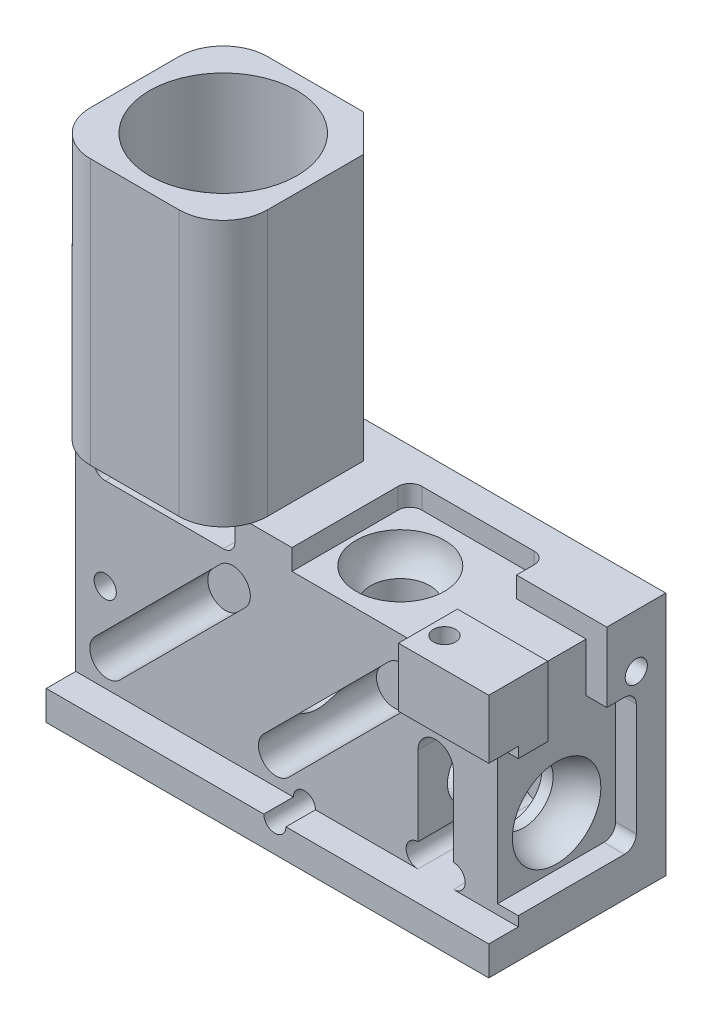
SolidWorks part; units mm, degrees
ref_plane "Front Plane" through (0, 0, 0) normal (0, 0, 1) x (1, 0, 0)
ref_plane "Top Plane" through (0, 0, 0) normal (0, 1, 0) x (1, 0, 0)
ref_plane "Right Plane" through (0, 0, 0) normal (1, 0, 0) x (0, 0, -1)
sketch "Sketch1" plane through (0, 0, 0) normal (0, 1, 0) x (1, 0, 0)
  line L1 (7.5, 3) -> (-7.5, 3)
  line L2 (7.5, 3) -> (7.5, -3)
  line L3 (7.5, -3) -> (-7.5, -3)
  line L4 (-7.5, 3) -> (-7.5, -3)
  line L5 (7.5, 3) -> (-7.5, -3) construction
  line L6 (7.5, -3) -> (-7.5, 3) construction
  point P0 (0, 0)
  dimension "D1" = 6
  dimension "D2" = 15
extrude "Main Body Ext" add sketch "Sketch1" along normal blind 8.3
sketch "Sketch8" plane through (0, 8.3, 0) normal (0, 1, 0) x (1, 0, 0)
  line L0 (-2.75, 3) -> (-1.5, 1.75)
  line L1 (-2.75, 3) -> (-7.5, 3)
  line L2 (-1.5, 1.75) -> (-1.5, -3)
  line L3 (-1.5, -3) -> (-7.5, -3)
  line L4 (-7.5, 3) -> (-7.5, -3)
  line L5 (-2.125, 2.375) -> (-7.5, -3) construction
  line L6 (-1.5, -3) -> (-7.5, 3) construction
  line L7 (-7.5, 3) -> (-7.5, -3) construction
  line L8 (0, 0) -> (-4.5, 0) construction
  point P0 (-4.5, 0)
  dimension "D1" = 6
  dimension "D2" = 6
  dimension "D3" = 1.25
  dimension "D4" = 3
extrude "Emission Path Ext" add sketch "Sketch8" along normal blind 9
sketch "Sketch3" plane through (0, 0, 0) normal (0, -1, 0) x (1, 0, 0)
  line L0 (-7.5, -3) -> (-7.5, 3) construction
  line L1 (0, 0) -> (-4.5, 0) construction
  circle A0 centre (-4.5, 0) radius 1.25
  dimension "D1" = 3
  dimension "D2" = 2.5
extrude "Emission and Grin Cut" cut sketch "Sketch3" against normal through all
sketch "Sketch4" plane through (7.5, 0, 0) normal (1, 0, 0) x (0, 0, -1)
  line L1 (-3, 0) -> (3, 0) construction
  circle A0 centre (0, 3) radius 1
  dimension "D1" = 2
  dimension "D2" = 3
extrude "Drum Lens Cut" cut sketch "Sketch4" against normal offset from surface (13 mm away) 2 up to face at (-7.5, 8.65, 0)
sketch "Sketch41" plane through (0, 8.3, 0) normal (0, 1, 0) x (1, 0, 0)
  line L1 (7.5, 3) -> (-2.75, 3) construction
  line L2 (-1.5, -3) -> (-1.5, 1.75) construction
  circle A0 centre (1.5, 0) radius 1
  dimension "D1" = 2
  dimension "D2" = 3
  dimension "D3" = 3
extrude "Addtl Light Source" cut sketch "Sketch41" against normal blind 5
sketch "Sketch5" plane through (0, 0, 3) normal (0, 0, 1) x (1, 0, 0)
  line L0 (-7.5, 0) -> (7.5, 0) construction
  line L1 (7.5, 8.3) -> (-7.5, 8.3)
  line L2 (7.5, 8.3) -> (7.5, 1)
  line L3 (7.5, 1) -> (-7.5, 1)
  line L4 (-7.5, 8.3) -> (-7.5, 1)
  line L5 (7.5, 8.3) -> (-7.5, 1) construction
  line L6 (7.5, 1) -> (-7.5, 8.3) construction
  line L7 (-1.5, 8.3) -> (7.5, 8.3) construction
  line L9 (7.5, 8.3) -> (7.5, 0) construction
  line L10 (-7.5, 17.3) -> (-7.5, 0) construction
  point P0 (0, 4.65)
  dimension "D1" = 1
extrude "FilterCover Cut1" cut sketch "Sketch5" against normal blind 1
sketch "Top-LED-Screw" plane through (0, 0, 2) normal (0, 0, 1) x (1, 0, 0)
  line L1 (7.5, 8.3) -> (4.44, 8.3)
  line L2 (7.5, 8.3) -> (7.5, 6.3)
  line L3 (7.5, 6.3) -> (4.44, 6.3)
  line L4 (4.44, 8.3) -> (4.44, 6.3)
  dimension "D1" = 2
  dimension "D2" = 3.06
extrude "Boss-Extrude1" add sketch "Top-LED-Screw" along normal blind 1
sketch "Sketch6" plane through (0, 0, 2) normal (0, 0, 1) x (1, 0, 0)
  line L0 (5.3, 4.5) -> (5.3, 1.8)
  line L1 (4.1, 4.5) -> (5.3, 4.5) construction
  line L2 (5.3, 1) -> (4.1, 1)
  line L3 (-7.5, 1) -> (7.5, 1) construction
  line L4 (-7.5, 8.3) -> (-7.5, 1) construction
  line L5 (-6.9, 7.9) -> (-6.9, 7.5)
  line L6 (4.1, 4.5) -> (4.1, 1.8)
  line L7 (-1.5, 8.3) -> (-7.5, 8.3) construction
  line L8 (-2.1, 7.9) -> (-2.1, 7.5)
  line L9 (-6, 1.5) -> (-6, 1) construction
  line L10 (-2.5, 8.3) -> (-6.5, 8.3)
  line L11 (-4.5, 3) -> (-4.5, 1) construction
  line L12 (-4.5, 3) -> (0.4851, 3) construction
  line L13 (-2.5, 7.1) -> (-6.5, 7.1)
  line L14 (-0.282, 1.5) -> (-0.282, 1) construction
  line L15 (-2.5, 8.3) -> (-6.5, 7.1) construction
  line L16 (-2.5, 7.1) -> (-6.5, 8.3) construction
  line L17 (4.1, 1.8) -> (5.3, 1.8) construction
  line L18 (-2.6059, 6.5912) -> (-6.8485, 2.3485)
  line L19 (7.5, 1) -> (7.5, 6.3) construction
  line L20 (-1.7574, 5.7426) -> (-6, 1.5)
  line L21 (-2.6059, 6.5912) -> (-6, 1.5) construction
  line L22 (-6.8485, 2.3485) -> (-1.7574, 5.7426) construction
  line L23 (1.826, 3.6081) -> (1.826, 1.6081) construction
  line L24 (1.826, 3.6081) -> (3.2165, 3.6081) construction
  line L25 (3.1121, 6.5912) -> (-1.1305, 2.3485)
  line L26 (3.9606, 5.7426) -> (-0.282, 1.5)
  line L27 (3.1121, 6.5912) -> (-0.282, 1.5) construction
  line L28 (-1.1305, 2.3485) -> (3.9606, 5.7426) construction
  line L33 (-2.5, 8.3) -> (1.102, 8.3) construction
  line L34 (1.102, 8.3) -> (1.102, 7.1) construction
  line L35 (1.102, 7.1) -> (-2.5, 7.1) construction
  line L36 (-6.5, 7.1) -> (-4.098, 7.1) construction
  line L37 (-4.098, 7.1) -> (-4.098, 8.3) construction
  line L38 (-4.098, 8.3) -> (-6.5, 8.3) construction
  line L39 (-6.5, 8.3) -> (-2.7284, 6.992) construction
  arc A0 (-2.5, 8.3) -> (-2.1, 7.9) centre (-2.5, 7.9) cw
  arc A1 (4.1, 4.5) -> (5.3, 4.5) centre (4.7, 4.5) cw
  arc A2 (-6.5, 8.3) -> (-6.9, 7.9) centre (-6.5, 7.9) ccw
  arc A3 (-2.6059, 6.5912) -> (-1.7574, 5.7426) centre (-2.1816, 6.1669) cw
  arc A4 (4.1, 1) -> (4.1, 1.8) centre (4.1, 1.4) cw
  arc A5 (-6.8485, 2.3485) -> (-6, 1.5) centre (-6.4243, 1.9243) ccw
  arc A6 (5.3, 1) -> (5.3, 1.8) centre (5.3, 1.4) ccw
  arc A7 (-6.5, 7.1) -> (-6.9, 7.5) centre (-6.5, 7.5) cw
  arc A8 (-2.5, 7.1) -> (-2.1, 7.5) centre (-2.5, 7.5) ccw
  arc A9 (3.1121, 6.5912) -> (3.9606, 5.7426) centre (3.5364, 6.1669) cw
  arc A10 (-1.1305, 2.3485) -> (-0.282, 1.5) centre (-0.7063, 1.9243) ccw
  point P5 (-4.5, 7.7)
  point P10 (-4.3029, 4.0456)
  point P21 (1.415, 4.0456)
  dimension "D10" = 0.5
  dimension "D5" = 2.2
  dimension "D8" = 0.4
  dimension "D11" = 0.4
  dimension "D12" = 0.4
  dimension "D1" = 1.2
  dimension "D2" = 45
  dimension "D3" = 3.5
  dimension "D4" = 1.2
  dimension "D6" = 2
  dimension "D7" = 4
  dimension "D9" = 3
  dimension "D13" = 1.2
  dimension "D14" = 3
  dimension "D15" = 6
  dimension "D16" = 45
  dimension "D17" = 0.5
  dimension "D18" = 1.2
  dimension "D19" = 2
  dimension "D20" = 6
extrude "FilterSet Cut2" cut sketch "Sketch6" against normal offset from surface (4 mm away) 1 up to face at (-0.0625, 9.2833, -3)
sketch "Sketch10" plane through (0, 17.3, 0) normal (0, 1, 0) x (1, 0, 0)
  line L0 (-4.5, 0) -> (-4.5, -3) construction
  line L1 (-7.5, -3) -> (-1.5, -3) construction
  line L3 (-4.5, 0) -> (-7.5, 0) construction
  line L4 (-7.5, 3) -> (-7.5, -3) construction
  circle A0 centre (-4.5, 0) radius 2.5
  dimension "D1" = 5
extrude "Emission Lens Cut" cut sketch "Sketch10" against normal offset from surface (8.5 mm away) 0.5 up to face at (-4.125, 8.3, 1.3125)
sketch "Sketch12" plane through (7.5, 0, 0) normal (1, 0, 0) x (0, 0, -1)
  line L0 (0, 3.635) -> (0, 0) construction
  line L1 (1.6, 5.94) -> (-1.6, 5.94)
  line L2 (1.6, 5.94) -> (1.6, 1.33) construction
  line L3 (-2, 1.33) -> (1.6, 1.33)
  line L4 (-1.6, 5.94) -> (-1.6, 1.33) construction
  line L5 (1.6, 5.94) -> (-1.6, 1.33) construction
  line L6 (1.6, 1.33) -> (-1.6, 5.94) construction
  line L7 (-3, 0) -> (3, 0) construction
  line L9 (-1.6, 5.94) -> (-2, 5.94)
  line L10 (-2, 1) -> (-2, 6.3) construction
  line L11 (-2, 5.94) -> (-2, 1.33)
  line L12 (2, 5.54) -> (2, 1.73)
  arc A1 (1.6, 5.94) -> (2, 5.54) centre (1.6, 5.54) cw
  arc A2 (1.6, 1.33) -> (2, 1.73) centre (1.6, 1.73) ccw
  circle A3 centre (0, 3) radius 1 construction
  point P0 (0, 3.635)
  dimension "D2" = 4.61
  dimension "D3" = 1.67
  dimension "D1" = 3.2
  dimension "D4" = 0.4
sketch "Sketch15" plane through (0, 0, 0) normal (0, -1, 0) x (1, 0, 0)
  line L0 (-6.25, 1.875) -> (-6.25, -1.875) construction
  line L2 (-1.5, 0) -> (-4.5, 0) construction
  line L3 (-4.5, 0) -> (-6.25, 0) construction
  circle A0 centre (-6.25, -1.875) radius 0.795
  circle A1 centre (-6.25, 1.875) radius 0.795
  circle A2 centre (-1.5, 0) radius 0.795
  dimension "D4" = 1.59
  dimension "D1" = 3.75
  dimension "D2" = 3
  dimension "D3" = 1.75
extrude "Magnets Cut" cut sketch "Sketch15" against normal blind 0.9
sketch "Sketch18" plane through (0, 0, 2) normal (0, 0, 1) x (1, 0, 0)
  line L0 (-7.5, 8.3) -> (-7.5, 1) construction
  line L1 (7.5, 1) -> (7.5, 6.3) construction
  line L2 (4.44, 8.3) -> (-1.5, 8.3) construction
  line L3 (-7.5, 0) -> (7.5, 0) construction
  line L7 (-7.5, 1) -> (4.1, 1) construction
  line L9 (-7.5, 1) -> (-7.5, 0) construction
  circle A0 centre (-6.5, 4) radius 0.375
  circle A1 centre (6, 5.8) radius 0.375
  circle A2 centre (0.25, 1) radius 0.375
  dimension "D1" = 0.75
  dimension "D2" = 1
  dimension "D3" = 2.5
  dimension "D4" = 1.5
  dimension "D5" = 3
  dimension "D6" = 1
  dimension "D7" = 7.75
extrude "Screw Holes Cut" cut sketch "Sketch18" against normal blind 2.5 and the other way through all
fillet "External Fillet 1" radius 1.5 2 edges at (-7.5, 8.65, -3)
sketch "Sketch28" plane through (0, 7.1, 0) normal (0, 1, 0) x (1, 0, 0)
  circle A0 centre (-4.5, 0) radius 1.5
  dimension "D1" = 3
extrude "Vertical-Path-Cut" cut sketch "Sketch28" against normal blind 4 and the other way through all
extrude "Cut-Extrude Original Light" cut sketch "Sketch12" against normal blind 0.7
sketch "Sketch44" plane through (0, 8.3, 0) normal (0, 1, 0) x (1, 0, 0)
  line L0 (-0.17, -2) -> (4.44, -2)
  line L1 (-0.17, -2) -> (-0.17, 1.6)
  line L2 (4.44, -2) -> (4.44, 1.6)
  line L3 (0.23, 2) -> (4.04, 2)
  line L6 (4.44, -2) -> (-1.5858, -2) construction
  circle A0 centre (1.5, 0) radius 1 construction
  arc A1 (4.44, 1.6) -> (4.04, 2) centre (4.04, 1.6) ccw
  arc A2 (-0.17, 1.6) -> (0.23, 2) centre (0.23, 1.6) cw
  point P10 (4.44, 2)
  point P13 (-0.17, 2)
  dimension "D3" = 1.67
  dimension "D4" = 0.4
  dimension "D5" = 0.4
  dimension "D1" = 4
  dimension "D2" = 4.61
extrude "Cut-Extrude Addtl Light" cut sketch "Sketch44" against normal blind 0.7
sketch "Sketch29" plane through (7.5, 0, 0) normal (1, 0, 0) x (0, 0, -1)
  line L0 (3, 8.3) -> (3, 0) construction
  line L1 (-3, 8.3) -> (3, 8.3) construction
  circle A0 centre (2, 6.5) radius 0.375
  circle A1 centre (0, 3) radius 1 construction
  dimension "D1" = 0.75
  dimension "D2" = 1
  dimension "D3" = 1.8
  dimension "D5" = 3.5
  dimension "D6" = 2
extrude "Side-LED-Screw" cut sketch "Sketch29" against normal blind 2.5
sketch "Sketch31" plane through (6.8, 0, 0) normal (1, 0, 0) x (0, 0, -1)
  circle A0 centre (0, 3) radius 1.6
  dimension "D1" = 3.2
sketch "Sketch32" plane through (7.5, 0, 0) normal (1, 0, 0) x (0, 0, -1)
  line L0 (-3, 8.3) -> (3, 8.3) construction
  line L1 (-1, 8.3) -> (1, 8.3)
  line L2 (-1, 8.3) -> (-1, 5.94)
  line L3 (-1, 5.94) -> (1, 5.94)
  line L4 (1, 8.3) -> (1, 5.94)
  line L5 (1.6, 5.94) -> (-2, 5.94) construction
  line L6 (-2, 5.94) -> (-2, 6.3) construction
  line L8 (3, 8.3) -> (3, 0) construction
  dimension "D1" = 1
  dimension "D2" = 2
extrude "Side-Wire-Slot-Cut" cut sketch "Sketch32" against normal up to surface (0.7 mm away) up to face at (6.8, 3.635, -0.5609)
sketch "Sketch45" plane through (0, 8.3, 0) normal (0, 1, 0) x (1, 0, 0)
  line L1 (4.44, -1) -> (6.8, -1)
  line L2 (4.44, -1) -> (4.44, 1)
  line L3 (4.44, 1) -> (6.8, 1)
  line L4 (6.8, -1) -> (6.8, 1)
  line L5 (4.44, -1) -> (6.8, 1) construction
  line L6 (4.44, 1) -> (6.8, -1) construction
  line L7 (6.8, 1) -> (6.8, -1) construction
  line L8 (4.44, -3) -> (4.44, 1.6) construction
  line L12 (6.8, -1) -> (7.5, -1) construction
  line L13 (6.8, 1) -> (7.5, 1) construction
extrude "Top-LED-slot" cut sketch "Sketch45" against normal blind 0.7
sketch "Sketch33" plane through (0, 0, 0) normal (0, 0, 1) x (1, 0, 0)
  line L0 (6.8, 3) -> (5.3, 3)
  line L1 (6.8, 1.4) -> (6.8, 4.6) construction
  line L2 (6.8, 3) -> (6.8, 4.5)
  arc A0 (5.3, 3) -> (6.8, 4.5) centre (6.8, 3) cw
  dimension "D2" = 1.5
revolve "Side-BallLens_Cut" cut sketch "Sketch33" angle 360 about L0
sketch "Sketch46" plane through (0, 7.6, 0) normal (0, 1, 0) x (1, 0, 0)
  circle A0 centre (1.5, 0) radius 1.5 construction
ref_plane "Plane1" through (1.5, 0, 0) normal (1, 0, 0) x (0, 0, -1)
sketch "Sketch47" plane through (1.5, 0, 0) normal (1, 0, 0) x (0, 0, -1)
  line L4 (-1.5, 7.6) -> (0, 7.6)
  line L5 (0, 7.6) -> (0, 6.1373)
  line L6 (1, 7.6) -> (-1, 7.6) construction
  arc A0 (0, 6.1373) -> (-1.5, 7.6) centre (0, 7.6378) cw
revolve "Top-BallLens_Cut" cut sketch "Sketch47" angle 360 about L5
sketch "Sketch36" plane through (0, 17.3, 0) normal (0, 1, 0) x (1, 0, 0)
  line L0 (-7.5, -1.5) -> (-7.5, -3)
  line L1 (-7.5, 1.5) -> (-7.5, -3) construction
  line L2 (-7.5, -3) -> (-6, -3)
  line L3 (-7.5, -3) -> (-3, -3) construction
  arc A0 (-7.5, -1.5) -> (-6, -3) centre (-6, -1.5) ccw
  dimension "D1" = 1.5
  dimension "D2" = 1.5
extrude "Cut-Extrude16" cut sketch "Sketch36" against normal up to surface (9 mm away) up to face at (-4.3971, 8.3, 1.2781)
sketch "Sketch37" plane through (0, 8.8, 0) normal (0, 1, 0) x (1, 0, 0)
  circle A0 centre (-4.5, 0) radius 2
  circle A1 centre (-4.5, 0) radius 1.5 construction
  dimension "D1" = 4
extrude "Cut-Extrude17" cut sketch "Sketch37" against normal up to next
sketch "Sketch51" plane through (0, 8.3, 0) normal (0, 1, 0) x (1, 0, 0)
  circle A0 centre (5, -2) radius 0.375
  circle A1 centre (1.5, 0) radius 1.5 construction
  dimension "D1" = 0.75
  dimension "D2" = 3.5
  dimension "D3" = 2
extrude "Top-LE-Screw" cut sketch "Sketch51" against normal blind 2.1
sketch "Notch" plane through (0, 0, 0) normal (0, -1, 0) x (1, 0, 0)
  line L0 (4.1286, -3) -> (3, -2.2476) construction
  line L1 (7.5, -3) -> (-6, -3) construction
  line L2 (3, -2.2476) -> (2.7532, -2.2476) construction
  line L3 (2.7532, -2.2476) -> (2.2516, -3) construction
  line L4 (3, -2.2476) -> (4.0396, -2.9406) construction
  line L5 (3, -2.2476) -> (2, -2.2476) construction
  line L6 (1.6516, -1.6476) -> (1.6516, -3)
  line L7 (5.2103, -3) -> (3.1817, -1.6476)
  line L8 (3.1817, -1.6476) -> (1.6516, -1.6476)
  line L9 (1.6516, -1.6476) -> (0.75, -3)
  line L10 (5.2103, -3) -> (1.6516, -3)
  line L12 (4.0396, -2.9406) -> (2.6528, -5.0208) construction
  line L13 (2.2516, -3) -> (2.2516, -2.2476) construction
  line L14 (2.2516, -2.2476) -> (2.7532, -2.2476) construction
  line M13 (-6, -3) -> (7.5, -3)
  dimension "D1" = 0.6
  dimension "D2" = 0.6
  dimension "D3" = 0.6
extrude "Cut-Extrude20" cut sketch "Notch" against normal blind 2 contours L7 L8 L6 M13 | L6 L9 M13 region at (2.9912, 0, -2.4137) region at (1.3511, 0, -2.5492)
